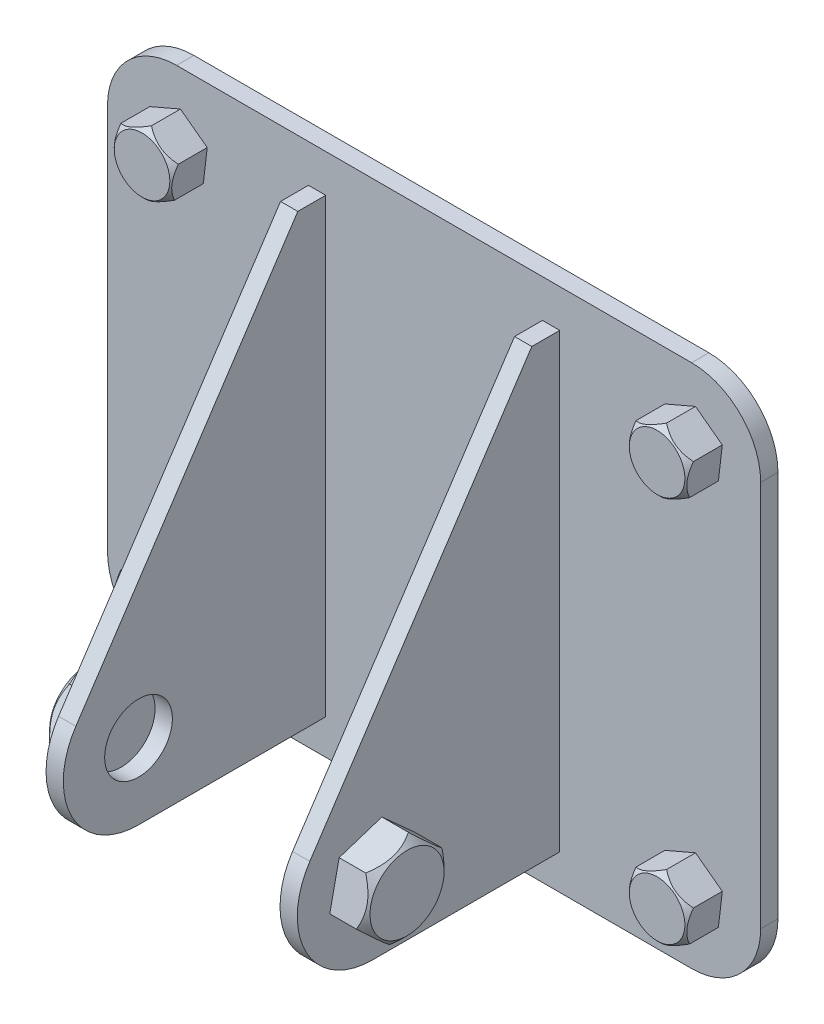
SolidWorks part; units mm, degrees
ref_plane "Front Plane" through (0, 0, 0) normal (0, 0, 1) x (1, 0, 0)
ref_plane "Top Plane" through (0, 0, 0) normal (0, 1, 0) x (1, 0, 0)
ref_plane "Right Plane" through (0, 0, 0) normal (1, 0, 0) x (0, 0, -1)
sketch "Sketch1" plane through (0, 0, 0) normal (0, 0, 1) x (1, 0, 0)
  line L1 (-89.5844, 69.6868) -> (99.5848, 69.6868)
  line L2 (-89.5844, 69.6868) -> (-89.5844, 221.6475)
  line L3 (-89.5844, 221.6475) -> (99.5848, 221.6475)
  line L4 (99.5848, 69.6868) -> (99.5848, 221.6475)
  line L5 (-89.5844, 69.6868) -> (99.5848, 221.6475) construction
  line L6 (-89.5844, 221.6475) -> (99.5848, 69.6868) construction
  point P0 (5.0002, 130.9195)
extrude "Boss-Extrude1" add sketch "Sketch1" along normal blind 5
sketch "Sketch2" plane through (0, 0, 5) normal (0, 0, 1) x (1, 0, 0)
  line L1 (36.3836, 210.6655) -> (41.3836, 210.6655)
  line L2 (-31.3832, 210.6655) -> (-31.3832, 79.8598)
  line L4 (-26.3832, 210.6655) -> (-26.3832, 79.8598)
  line L6 (36.3836, 79.8598) -> (41.3836, 79.8598)
  line L7 (36.3836, 210.6655) -> (36.3836, 79.8598)
  line L9 (41.3836, 210.6655) -> (41.3836, 79.8598)
  line L11 (-31.3832, 210.6655) -> (-26.3832, 210.6655)
  line L13 (-31.3832, 79.8598) -> (-26.3832, 79.8598)
extrude "Boss-Extrude2" add sketch "Sketch2" along normal blind 76
sketch "Sketch3" plane through (-31.3832, 0, 0) normal (-1, 0, 0) x (0, 0, 1)
  line L0 (59.22, 79.8598) -> (59.22, 69.5629)
  line L1 (13.0868, 210.6655) -> (77.3743, 113.6726)
  line L2 (81, 210.6655) -> (5, 210.6655) construction
  line L5 (93.4988, 226.993) -> (13.0868, 210.6655)
  line L6 (59.22, 69.5629) -> (98.4593, 69.5629)
  line L7 (98.4593, 69.5629) -> (93.4988, 226.993)
  arc A0 (59.22, 79.8598) -> (77.3743, 113.6726) centre (59.22, 101.6398) ccw
  circle A1 centre (59.22, 101.6398) radius 9.8101
extrude "Cut-Extrude1" cut sketch "Sketch3" against normal blind 244
fillet "Fillet1" radius 20 4 edges at (-89.5844, 69.6868, 2.5) (99.5848, 69.6868, 2.5) (99.5848, 221.6475, 2.5) (-89.5844, 221.6475, 2.5)
sketch "Sketch4" plane through (-31.3832, 0, 0) normal (-1, 0, 0) x (0, 0, 1)
  line L1 (66.574, 112.5828) -> (53.4201, 113.4801)
  line L2 (53.4201, 113.4801) -> (46.0661, 102.537)
  line L3 (46.0661, 102.537) -> (51.866, 90.6968)
  line L4 (51.866, 90.6968) -> (65.02, 89.7996)
  line L5 (65.02, 89.7996) -> (72.3739, 100.7426)
  line L6 (72.3739, 100.7426) -> (66.574, 112.5828)
  circle A0 centre (59.22, 101.6398) radius 11.4181 construction
extrude "Boss-Extrude3" add sketch "Sketch4" along normal blind 10
sketch "Sketch5" plane through (-41.3832, 0, 0) normal (-1, 0, 0) x (0, 0, 1)
  circle A0 centre (59.22, 101.6398) radius 10.7552
  circle A1 centre (59.22, 101.6398) radius 15.3605
extrude "Cut-Extrude2" cut sketch "Sketch5" against normal blind 10 draft 45
sketch "Sketch6" plane through (41.3836, 0, 0) normal (1, 0, 0) x (0, 0, -1)
  line L1 (-46.8418, 105.6527) -> (-56.5061, 114.3661)
  line L2 (-56.5061, 114.3661) -> (-68.8843, 110.3532)
  line L3 (-68.8843, 110.3532) -> (-71.5982, 97.627)
  line L4 (-71.5982, 97.627) -> (-61.9339, 88.9136)
  line L5 (-61.9339, 88.9136) -> (-49.5557, 92.9264)
  line L6 (-49.5557, 92.9264) -> (-46.8418, 105.6527)
  circle A0 centre (-59.22, 101.6398) radius 11.2691 construction
extrude "Boss-Extrude4" add sketch "Sketch6" along normal blind 10
sketch "Sketch8" plane through (51.3836, 0, 0) normal (1, 0, 0) x (0, 0, -1)
  circle A0 centre (-59.22, 101.6398) radius 10.7268
  circle A1 centre (-59.22, 101.6398) radius 15.2761
extrude "Cut-Extrude3" cut sketch "Sketch8" against normal blind 10 draft 45
sketch "Sketch9" plane through (0, 0, 5) normal (0, 0, 1) x (1, 0, 0)
  line L0 (80.709, 211.2544) -> (71.827, 207.4245)
  line L1 (-60.7025, 205.4773) -> (-68.4602, 211.2544)
  line L2 (-68.4602, 211.2544) -> (-77.3422, 207.4245)
  line L3 (-77.3422, 207.4245) -> (-78.4664, 197.8176)
  line L4 (-78.4664, 197.8176) -> (-70.7086, 192.0405)
  line L5 (-70.7086, 192.0405) -> (-61.8267, 195.8704)
  line L6 (-61.8267, 195.8704) -> (-60.7025, 205.4773)
  line L7 (70.7028, 197.8176) -> (78.4606, 192.0405)
  line L8 (87.3425, 195.8704) -> (88.4667, 205.4773)
  line L9 (88.4667, 205.4773) -> (80.709, 211.2544)
  line L10 (71.827, 207.4245) -> (70.7028, 197.8176)
  line L11 (78.4606, 192.0405) -> (87.3425, 195.8704)
  line L12 (80.709, 99.2938) -> (71.827, 95.4639)
  line L13 (70.7028, 85.857) -> (78.4606, 80.0799)
  line L14 (87.3425, 83.9098) -> (88.4667, 93.5167)
  line L15 (88.4667, 93.5167) -> (80.709, 99.2938)
  line L16 (71.827, 95.4639) -> (70.7028, 85.857)
  line L17 (78.4606, 80.0799) -> (87.3425, 83.9098)
  line L18 (-68.4602, 99.2938) -> (-77.3422, 95.4639)
  line L19 (-78.4664, 85.857) -> (-70.7086, 80.0799)
  line L20 (-61.8267, 83.9098) -> (-60.7025, 93.5167)
  line L21 (-60.7025, 93.5167) -> (-68.4602, 99.2938)
  line L22 (-77.3422, 95.4639) -> (-78.4664, 85.857)
  line L23 (-70.7086, 80.0799) -> (-61.8267, 83.9098)
  circle A0 centre (-69.5844, 201.6475) radius 8.3766 construction
  circle A1 centre (79.5848, 201.6475) radius 8.3766 construction
  circle A2 centre (79.5848, 89.6868) radius 8.3766 construction
  circle A3 centre (-69.5844, 89.6868) radius 8.3766 construction
extrude "Boss-Extrude5" add sketch "Sketch9" along normal blind 10
sketch "Sketch10" plane through (0, 0, 15) normal (0, 0, 1) x (1, 0, 0)
  circle A0 centre (-69.5844, 201.6475) radius 8.0509
  circle A1 centre (-69.5844, 201.6475) radius 11.3003
  circle A2 centre (79.5848, 201.6475) radius 8.0509
  circle A3 centre (79.5848, 201.6475) radius 11.3003
  circle A4 centre (79.5848, 89.6868) radius 8.0509
  circle A5 centre (79.5848, 89.6868) radius 11.3003
  circle A6 centre (-69.5844, 89.6868) radius 8.0509
  circle A7 centre (-69.5844, 89.6868) radius 11.3003
extrude "Cut-Extrude5" cut sketch "Sketch10" against normal blind 10 draft 45
